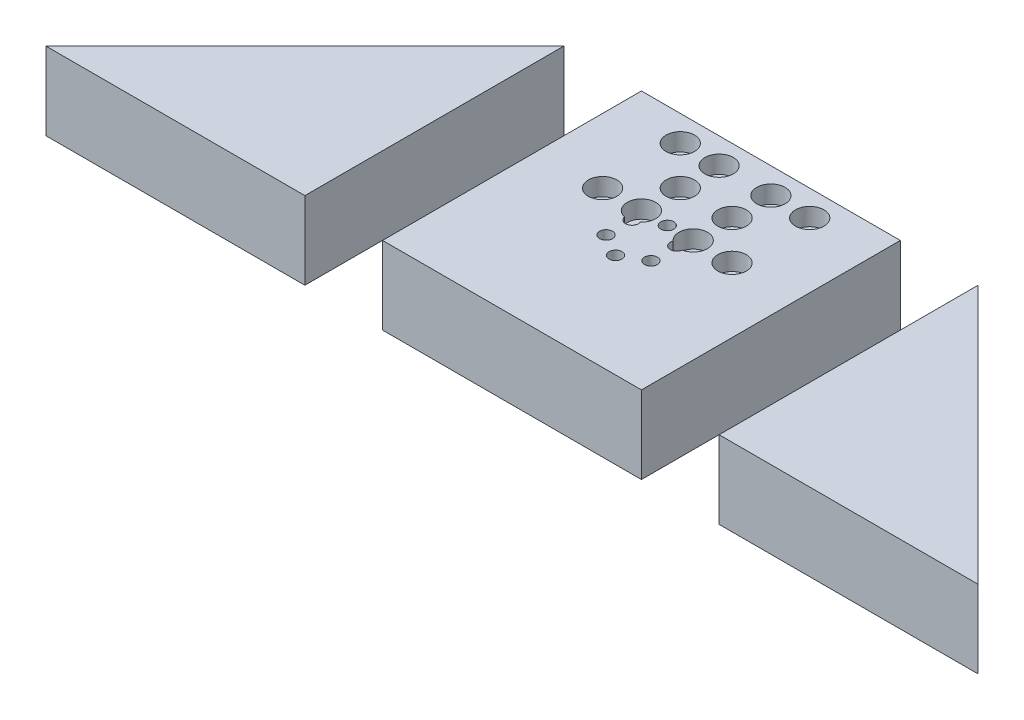
SolidWorks part; units mm, degrees
ref_plane "前视基准面" through (0, 0, 0) normal (0, 0, 1) x (1, 0, 0)
ref_plane "上视基准面" through (0, 0, 0) normal (0, 1, 0) x (1, 0, 0)
ref_plane "右视基准面" through (0, 0, 0) normal (1, 0, 0) x (0, 0, -1)
other "Configuration Table"
sketch "草图1" plane through (0, 0, 0) normal (0, 1, 0) x (1, 0, 0)
  line L0 (80, 50) -> (80, -50)
  line L1 (50, -50) -> (-50, -50)
  line L2 (50, -50) -> (50, 50)
  line L3 (50, 50) -> (-50, 50)
  line L4 (-50, -50) -> (-50, 50)
  line L5 (50, -50) -> (-50, 50) construction
  line L6 (50, 50) -> (-50, -50) construction
  line L7 (80, -50) -> (180, -50)
  line L8 (180, -50) -> (80, 50)
  point P0 (0, 0)
  point P8 (0, 0)
  dimension "D1" = 100
  dimension "D2" = 30
extrude "凸台-拉伸1" add sketch "草图1" along normal blind 30
hole_wizard "M6 六角圆柱头螺钉的柱形沉头孔1" positions "草图2" profile "草图3" counterbore size "M6" standard "GB" end condition through all
sketch "草图2" plane through (0, 30, 0) normal (0, 1, 0) x (1, 0, 0)
  line L0 (50, 50) -> (-50, 50) construction
  line L3 (-50, 50) -> (-50, -50) construction
  point P0 (-25, 10)
  dimension "D1" = 40
  dimension "D2" = 25
sketch "草图3" plane through (-25, 30, -10) normal (1, 0, 0) x (0, 0, 1)
  line L0 (0, 0) -> (0, 30)
  line L1 (0, 30) -> (3.3, 30)
  line L3 (3.3, 30) -> (3.3, 6.8)
  line L4 (3.3, 6.8) -> (5.5, 6.8)
  line L5 (5.5, 6.8) -> (5.5, 0)
  line L7 (5.5, 0) -> (0, 0)
  line L11 (0, -6.35) -> (0, 107.95) construction
  dimension "通孔孔直径" = 6.6
  dimension "通孔孔深度" = 30
  dimension "柱形沉头孔直径" = 11
  dimension "柱形沉头孔深度" = 6.8
hole_wizard "M6 螺纹孔1" positions "草图4" profile "草图5" tap size "M6" standard "GB" end condition through all
sketch "草图4" plane through (0, 30, 0) normal (0, 1, 0) x (1, 0, 0)
  line L0 (-25, 10) -> (0, 10)
  line L2 (0, 10) -> (0, 0)
  point P0 (0, 10)
sketch "草图5" plane through (0, 30, -10) normal (1, 0, 0) x (0, 0, 1)
  line L0 (0, 0) -> (0, 30)
  line L1 (0, 30) -> (2.5, 30)
  line L2 (2.5, 30) -> (2.5, 0)
  line L5 (2.5, 0) -> (0, 0)
  line L11 (0, -6.35) -> (0, 107.95) construction
  dimension "通孔螺纹孔钻头直径" = 5
  dimension "通孔螺纹孔钻头深度" = 30
cosmetic thread "孔螺蚊线1" parameters "D2"=6
pattern_linear "阵列(线性)1" count 2 spacing 15 along (1, 0, 0) count 3 spacing 15 along (0, 0, -1) skipping (0, 1) of "M6 六角圆柱头螺钉的柱形沉头孔1"
ref_axis "基准轴1" through (0, 0, 0) along (0, 1, 0)
pattern_circular "阵列(圆周)1" count 6 over 360 about axis through (0, 0, 0) along (0, 1, 0) of "M6 螺纹孔1"
mirror "镜向1" about plane through (0, 0, 0) normal (1, 0, 0) of "阵列(线性)1"
mirror "镜向3" about plane through (0, 0, 0) normal (1, 0, 0) of bodies 107
